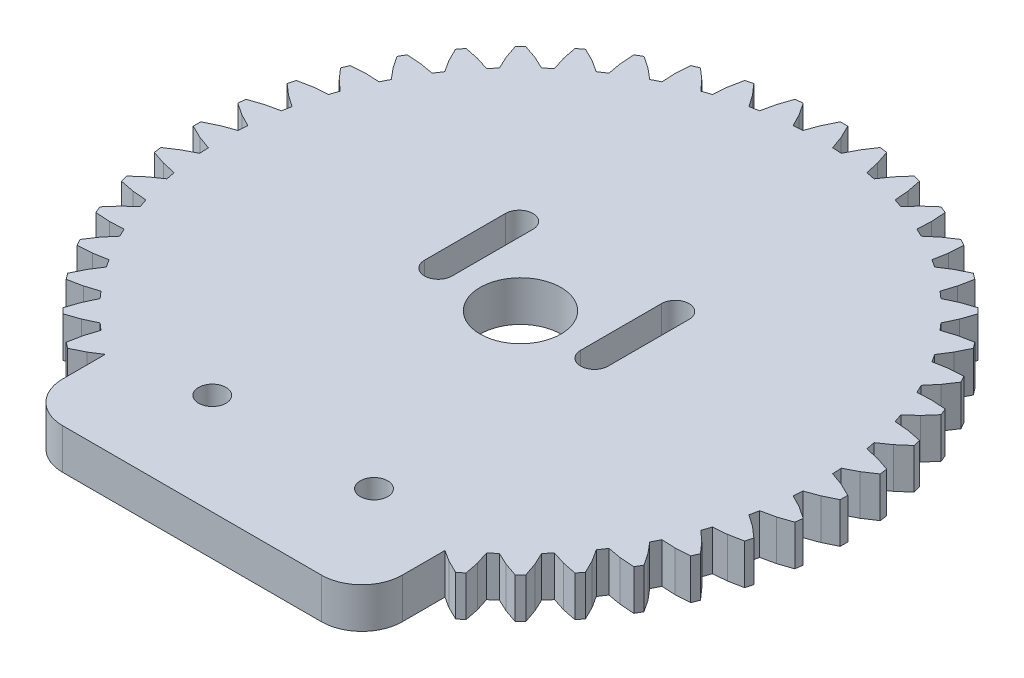
SolidWorks part; units mm, degrees
material "Acrylic (Medium-high impact)"
ref_plane "Front Plane" through (0, 0, 0) normal (0, 0, 1) x (1, 0, 0)
ref_plane "Top Plane" through (0, 0, 0) normal (0, 1, 0) x (1, 0, 0)
ref_plane "Right Plane" through (0, 0, 0) normal (1, 0, 0) x (0, 0, -1)
sketch "Sketch2" plane through (0, 0, 0) normal (0, 1, 0) x (1, 0, 0)
  line L0 (83.8835, 67.191) -> (85.5092, 66.6061)
  line L1 (85.5092, 66.6061) -> (87.1271, 65.8138)
  line L2 (87.1271, 65.8138) -> (87.1271, 64.8854)
  line L3 (87.1271, 64.8854) -> (85.5092, 64.0931)
  line L4 (85.5092, 64.0931) -> (83.8835, 63.5083)
  line L5 (83.8835, 63.5083) -> (83.8095, 62.3776)
  line L6 (83.8095, 62.3776) -> (85.3448, 61.5855)
  line L7 (85.3448, 61.5855) -> (86.8456, 60.5888)
  line L8 (86.8456, 60.5888) -> (86.7243, 59.6683)
  line L9 (86.7243, 59.6683) -> (85.0168, 59.094)
  line L10 (85.0168, 59.094) -> (83.3288, 58.7263)
  line L11 (83.3288, 58.7263) -> (83.1077, 57.615)
  line L12 (83.1077, 57.615) -> (84.5266, 56.6293)
  line L13 (84.5266, 56.6293) -> (85.8844, 55.4453)
  line L14 (85.8844, 55.4453) -> (85.6441, 54.5485)
  line L15 (85.6441, 54.5485) -> (83.8761, 54.202)
  line L16 (83.8761, 54.202) -> (82.1545, 54.0577)
  line L17 (82.1545, 54.0577) -> (81.7903, 52.9848)
  line L18 (81.7903, 52.9848) -> (83.0684, 51.8222)
  line L19 (83.0684, 51.8222) -> (84.26, 50.4711)
  line L20 (84.26, 50.4711) -> (83.9048, 49.6134)
  line L21 (83.9048, 49.6134) -> (82.1066, 49.5006)
  line L22 (82.1066, 49.5006) -> (80.3809, 49.5823)
  line L23 (80.3809, 49.5823) -> (79.8799, 48.5661)
  line L24 (79.8799, 48.5661) -> (80.9952, 47.2468)
  line L25 (80.9952, 47.2468) -> (82.0003, 45.7516)
  line L26 (82.0003, 45.7516) -> (81.5361, 44.9476)
  line L27 (81.5361, 44.9476) -> (79.7387, 45.0704)
  line L28 (79.7387, 45.0704) -> (78.0384, 45.3766)
  line L29 (78.0384, 45.3766) -> (77.4089, 44.4346)
  line L30 (77.4089, 44.4346) -> (78.3426, 42.9809)
  line L31 (78.3426, 42.9809) -> (79.1439, 41.3674)
  line L32 (79.1439, 41.3674) -> (78.5788, 40.6309)
  line L33 (78.5788, 40.6309) -> (76.8128, 40.9873)
  line L34 (76.8128, 40.9873) -> (75.167, 41.5128)
  line L35 (75.167, 41.5128) -> (74.4199, 40.6609)
  line L36 (74.4199, 40.6609) -> (75.1558, 39.0979)
  line L37 (75.1558, 39.0979) -> (75.7397, 37.3936)
  line L38 (75.7397, 37.3936) -> (75.0832, 36.737)
  line L39 (75.0832, 36.737) -> (73.3788, 37.3209)
  line L40 (73.3788, 37.3209) -> (71.8158, 38.0569)
  line L41 (71.8158, 38.0569) -> (70.9639, 37.3097)
  line L42 (70.9639, 37.3097) -> (71.4895, 35.6639)
  line L43 (71.4895, 35.6639) -> (71.8459, 33.898)
  line L44 (71.8459, 33.898) -> (71.1093, 33.3328)
  line L45 (71.1093, 33.3328) -> (69.4958, 34.1341)
  line L46 (69.4958, 34.1341) -> (68.0421, 35.0679)
  line L47 (68.0421, 35.0679) -> (67.1001, 34.4384)
  line L48 (67.1001, 34.4384) -> (67.4064, 32.738)
  line L49 (67.4064, 32.738) -> (67.5292, 30.9407)
  line L50 (67.5292, 30.9407) -> (66.7251, 30.4764)
  line L51 (66.7251, 30.4764) -> (65.23, 31.4815)
  line L52 (65.23, 31.4815) -> (63.9107, 32.5969)
  line L53 (63.9107, 32.5969) -> (62.8945, 32.0958)
  line L54 (62.8945, 32.0958) -> (62.9762, 30.3701)
  line L55 (62.9762, 30.3701) -> (62.8633, 28.572)
  line L56 (62.8633, 28.572) -> (62.0056, 28.2167)
  line L57 (62.0056, 28.2167) -> (60.6545, 29.4083)
  line L58 (60.6545, 29.4083) -> (59.4919, 30.6864)
  line L59 (59.4919, 30.6864) -> (58.419, 30.3222)
  line L60 (58.419, 30.3222) -> (58.2748, 28.6006)
  line L61 (58.2748, 28.6006) -> (57.9283, 26.8327)
  line L62 (57.9283, 26.8327) -> (57.0315, 26.5924)
  line L63 (57.0315, 26.5924) -> (55.8474, 27.9502)
  line L64 (55.8474, 27.9502) -> (54.8618, 29.369)
  line L65 (54.8618, 29.369) -> (53.7504, 29.1479)
  line L66 (53.7504, 29.1479) -> (53.3827, 27.4599)
  line L67 (53.3827, 27.4599) -> (52.8084, 25.7524)
  line L68 (52.8084, 25.7524) -> (51.888, 25.6311)
  line L69 (51.888, 25.6311) -> (50.8913, 27.1319)
  line L70 (50.8913, 27.1319) -> (50.0992, 28.6672)
  line L71 (50.0992, 28.6672) -> (48.9685, 28.5932)
  line L72 (48.9685, 28.5932) -> (48.3836, 26.9675)
  line L73 (48.3836, 26.9675) -> (47.5914, 25.3496)
  line L74 (47.5914, 25.3496) -> (46.6629, 25.3496)
  line L75 (46.6629, 25.3496) -> (45.8707, 26.9675)
  line L76 (45.8707, 26.9675) -> (45.2858, 28.5932)
  line L77 (45.2858, 28.5932) -> (44.1551, 28.6672)
  line L78 (44.1551, 28.6672) -> (43.363, 27.1319)
  line L79 (43.363, 27.1319) -> (42.3663, 25.6311)
  line L80 (42.3663, 25.6311) -> (41.4459, 25.7524)
  line L81 (41.4459, 25.7524) -> (40.8715, 27.4599)
  line L82 (40.8715, 27.4599) -> (40.5038, 29.1479)
  line L83 (40.5038, 29.1479) -> (39.3925, 29.369)
  line L84 (39.3925, 29.369) -> (38.4068, 27.9502)
  line L85 (38.4068, 27.9502) -> (37.2228, 26.5924)
  line L86 (37.2228, 26.5924) -> (36.326, 26.8327)
  line L87 (36.326, 26.8327) -> (35.9795, 28.6006)
  line L88 (35.9795, 28.6006) -> (35.8352, 30.3222)
  line L89 (35.8352, 30.3222) -> (34.7624, 30.6864)
  line L90 (34.7624, 30.6864) -> (33.5998, 29.4083)
  line L91 (33.5998, 29.4083) -> (32.2487, 28.2167)
  line L92 (32.2487, 28.2167) -> (31.3909, 28.572)
  line L93 (31.3909, 28.572) -> (31.2781, 30.3701)
  line L94 (31.2781, 30.3701) -> (31.3598, 32.0958)
  line L95 (31.3598, 32.0958) -> (30.3436, 32.5969)
  line L96 (30.3436, 32.5969) -> (29.0243, 31.4815)
  line L97 (29.0243, 31.4815) -> (27.5292, 30.4764)
  line L98 (27.5292, 30.4764) -> (26.7251, 30.9407)
  line L99 (26.7251, 30.9407) -> (26.8479, 32.738)
  line L100 (26.8479, 32.738) -> (27.1541, 34.4384)
  line L101 (27.1541, 34.4384) -> (26.2121, 35.0679)
  line L102 (26.2121, 35.0679) -> (24.7585, 34.1341)
  line L103 (24.7585, 34.1341) -> (23.1449, 33.3328)
  line L104 (23.1449, 33.3328) -> (22.4084, 33.898)
  line L105 (22.4084, 33.898) -> (22.7648, 35.6639)
  line L106 (22.7648, 35.6639) -> (23.2904, 37.3097)
  line L107 (23.2904, 37.3097) -> (22.4384, 38.0569)
  line L108 (22.4384, 38.0569) -> (20.8754, 37.3209)
  line L109 (20.8754, 37.3209) -> (19.1711, 36.737)
  line L110 (19.1711, 36.737) -> (18.5146, 37.3936)
  line L111 (18.5146, 37.3936) -> (19.0984, 39.0979)
  line L112 (19.0984, 39.0979) -> (19.8344, 40.6609)
  line L113 (19.8344, 40.6609) -> (19.0872, 41.5128)
  line L114 (19.0872, 41.5128) -> (17.4414, 40.9873)
  line L115 (17.4414, 40.9873) -> (15.6755, 40.6309)
  line L116 (15.6755, 40.6309) -> (15.1103, 41.3674)
  line L117 (15.1103, 41.3674) -> (15.9116, 42.9809)
  line L118 (15.9116, 42.9809) -> (16.8454, 44.4346)
  line L119 (16.8454, 44.4346) -> (16.2159, 45.3766)
  line L120 (16.2159, 45.3766) -> (14.5155, 45.0704)
  line L121 (14.5155, 45.0704) -> (12.7182, 44.9476)
  line L122 (12.7182, 44.9476) -> (12.2539, 45.7516)
  line L123 (12.2539, 45.7516) -> (13.2591, 47.2468)
  line L124 (13.2591, 47.2468) -> (14.3744, 48.5661)
  line L125 (14.3744, 48.5661) -> (13.8733, 49.5823)
  line L126 (13.8733, 49.5823) -> (12.1476, 49.5006)
  line L127 (12.1476, 49.5006) -> (10.3495, 49.6134)
  line L128 (10.3495, 49.6134) -> (9.9942, 50.4711)
  line L129 (9.9942, 50.4711) -> (11.1858, 51.8222)
  line L130 (11.1858, 51.8222) -> (12.4639, 52.9848)
  line L131 (12.4639, 52.9848) -> (12.0997, 54.0577)
  line L132 (12.0997, 54.0577) -> (10.3781, 54.202)
  line L133 (10.3781, 54.202) -> (8.6102, 54.5485)
  line L134 (8.6102, 54.5485) -> (8.3699, 55.4453)
  line L135 (8.3699, 55.4453) -> (9.7277, 56.6293)
  line L136 (9.7277, 56.6293) -> (11.1465, 57.615)
  line L137 (11.1465, 57.615) -> (10.9255, 58.7263)
  line L138 (10.9255, 58.7263) -> (9.2374, 59.094)
  line L139 (9.2374, 59.094) -> (7.5299, 59.6683)
  line L140 (7.5299, 59.6683) -> (7.4086, 60.5888)
  line L141 (7.4086, 60.5888) -> (8.9094, 61.5855)
  line L142 (8.9094, 61.5855) -> (10.4448, 62.3776)
  line L143 (10.4448, 62.3776) -> (10.3707, 63.5083)
  line L144 (10.3707, 63.5083) -> (8.745, 64.0931)
  line L145 (8.745, 64.0931) -> (7.1271, 64.8854)
  line L146 (7.1271, 64.8854) -> (7.1271, 65.8138)
  line L147 (7.1271, 65.8138) -> (8.745, 66.6061)
  line L148 (8.745, 66.6061) -> (10.3707, 67.191)
  line L149 (10.3707, 67.191) -> (10.4448, 68.3216)
  line L150 (10.4448, 68.3216) -> (8.9094, 69.1138)
  line L151 (8.9094, 69.1138) -> (7.4086, 70.1105)
  line L152 (7.4086, 70.1105) -> (7.5299, 71.0309)
  line L153 (7.5299, 71.0309) -> (9.2374, 71.6052)
  line L154 (9.2374, 71.6052) -> (10.9255, 71.9729)
  line L155 (10.9255, 71.9729) -> (11.1465, 73.0842)
  line L156 (11.1465, 73.0842) -> (9.7277, 74.0699)
  line L157 (9.7277, 74.0699) -> (8.3699, 75.254)
  line L158 (8.3699, 75.254) -> (8.6102, 76.1508)
  line L159 (8.6102, 76.1508) -> (10.3781, 76.4973)
  line L160 (10.3781, 76.4973) -> (12.0997, 76.6415)
  line L161 (12.0997, 76.6415) -> (12.4639, 77.7144)
  line L162 (12.4639, 77.7144) -> (11.1858, 78.877)
  line L163 (11.1858, 78.877) -> (9.9942, 80.2281)
  line L164 (9.9942, 80.2281) -> (10.3495, 81.0858)
  line L165 (10.3495, 81.0858) -> (12.1476, 81.1987)
  line L166 (12.1476, 81.1987) -> (13.8733, 81.117)
  line L167 (13.8733, 81.117) -> (14.3744, 82.1332)
  line L168 (14.3744, 82.1332) -> (13.2591, 83.4525)
  line L169 (13.2591, 83.4525) -> (12.2539, 84.9476)
  line L170 (12.2539, 84.9476) -> (12.7182, 85.7516)
  line L171 (12.7182, 85.7516) -> (14.5155, 85.6289)
  line L172 (14.5155, 85.6289) -> (16.2159, 85.3226)
  line L173 (16.2159, 85.3226) -> (16.8454, 86.2646)
  line L174 (16.8454, 86.2646) -> (15.9116, 87.7183)
  line L175 (15.9116, 87.7183) -> (15.1103, 89.3318)
  line L176 (15.1103, 89.3318) -> (15.6755, 90.0684)
  line L177 (15.6755, 90.0684) -> (17.4414, 89.712)
  line L178 (17.4414, 89.712) -> (19.0872, 89.1864)
  line L179 (19.0872, 89.1864) -> (19.8344, 90.0383)
  line L180 (19.8344, 90.0383) -> (19.0984, 91.6013)
  line L181 (19.0984, 91.6013) -> (18.5146, 93.3057)
  line L182 (18.5146, 93.3057) -> (19.1711, 93.9622)
  line L183 (19.1711, 93.9622) -> (20.8754, 93.3783)
  line L184 (20.8754, 93.3783) -> (22.4384, 92.6424)
  line L185 (22.4384, 92.6424) -> (23.2904, 93.3895)
  line L186 (23.2904, 93.3895) -> (22.7648, 95.0353)
  line L187 (22.7648, 95.0353) -> (22.4084, 96.8013)
  line L188 (22.4084, 96.8013) -> (23.1449, 97.3664)
  line L189 (23.1449, 97.3664) -> (24.7585, 96.5651)
  line L190 (24.7585, 96.5651) -> (26.2121, 95.6314)
  line L191 (26.2121, 95.6314) -> (27.1541, 96.2609)
  line L192 (27.1541, 96.2609) -> (26.8479, 97.9612)
  line L193 (26.8479, 97.9612) -> (26.7251, 99.7586)
  line L194 (26.7251, 99.7586) -> (27.5292, 100.2228)
  line L195 (27.5292, 100.2228) -> (29.0243, 99.2177)
  line L196 (29.0243, 99.2177) -> (30.3436, 98.1023)
  line L197 (30.3436, 98.1023) -> (31.3598, 98.6034)
  line L198 (31.3598, 98.6034) -> (31.2781, 100.3291)
  line L199 (31.2781, 100.3291) -> (31.3909, 102.1272)
  line L200 (31.3909, 102.1272) -> (32.2487, 102.4825)
  line L201 (32.2487, 102.4825) -> (33.5998, 101.2909)
  line L202 (33.5998, 101.2909) -> (34.7624, 100.0128)
  line L203 (34.7624, 100.0128) -> (35.8352, 100.377)
  line L204 (35.8352, 100.377) -> (35.9795, 102.0986)
  line L205 (35.9795, 102.0986) -> (36.326, 103.8666)
  line L206 (36.326, 103.8666) -> (37.2228, 104.1068)
  line L207 (37.2228, 104.1068) -> (38.4068, 102.7491)
  line L208 (38.4068, 102.7491) -> (39.3925, 101.3302)
  line L209 (39.3925, 101.3302) -> (40.5038, 101.5513)
  line L210 (40.5038, 101.5513) -> (40.8715, 103.2393)
  line L211 (40.8715, 103.2393) -> (41.4459, 104.9468)
  line L212 (41.4459, 104.9468) -> (42.3663, 105.0681)
  line L213 (42.3663, 105.0681) -> (43.363, 103.5673)
  line L214 (43.363, 103.5673) -> (44.1551, 102.032)
  line L215 (44.1551, 102.032) -> (45.2858, 102.106)
  line L216 (45.2858, 102.106) -> (45.8707, 103.7317)
  line L217 (45.8707, 103.7317) -> (46.6629, 105.3496)
  line L218 (46.6629, 105.3496) -> (47.5914, 105.3496)
  line L219 (47.5914, 105.3496) -> (48.3836, 103.7317)
  line L220 (48.3836, 103.7317) -> (48.9685, 102.106)
  line L221 (48.9685, 102.106) -> (50.0992, 102.032)
  line L222 (50.0992, 102.032) -> (50.8913, 103.5673)
  line L223 (50.8913, 103.5673) -> (51.888, 105.0681)
  line L224 (51.888, 105.0681) -> (52.8084, 104.9468)
  line L225 (52.8084, 104.9468) -> (53.3827, 103.2393)
  line L226 (53.3827, 103.2393) -> (53.7504, 101.5513)
  line L227 (53.7504, 101.5513) -> (54.8618, 101.3302)
  line L228 (54.8618, 101.3302) -> (55.8474, 102.7491)
  line L229 (55.8474, 102.7491) -> (57.0315, 104.1068)
  line L230 (57.0315, 104.1068) -> (57.9283, 103.8666)
  line L231 (57.9283, 103.8666) -> (58.2748, 102.0986)
  line L232 (58.2748, 102.0986) -> (58.419, 100.377)
  line L233 (58.419, 100.377) -> (59.4919, 100.0128)
  line L234 (59.4919, 100.0128) -> (60.6545, 101.2909)
  line L235 (60.6545, 101.2909) -> (62.0056, 102.4825)
  line L236 (62.0056, 102.4825) -> (62.8633, 102.1272)
  line L237 (62.8633, 102.1272) -> (62.9762, 100.3291)
  line L238 (62.9762, 100.3291) -> (62.8945, 98.6034)
  line L239 (62.8945, 98.6034) -> (63.9107, 98.1023)
  line L240 (63.9107, 98.1023) -> (65.23, 99.2177)
  line L241 (65.23, 99.2177) -> (66.7251, 100.2228)
  line L242 (66.7251, 100.2228) -> (67.5292, 99.7586)
  line L243 (67.5292, 99.7586) -> (67.4064, 97.9612)
  line L244 (67.4064, 97.9612) -> (67.1001, 96.2609)
  line L245 (67.1001, 96.2609) -> (68.0421, 95.6314)
  line L246 (68.0421, 95.6314) -> (69.4958, 96.5651)
  line L247 (69.4958, 96.5651) -> (71.1093, 97.3664)
  line L248 (71.1093, 97.3664) -> (71.8459, 96.8013)
  line L249 (71.8459, 96.8013) -> (71.4895, 95.0353)
  line L250 (71.4895, 95.0353) -> (70.9639, 93.3895)
  line L251 (70.9639, 93.3895) -> (71.8158, 92.6424)
  line L252 (71.8158, 92.6424) -> (73.3788, 93.3783)
  line L253 (73.3788, 93.3783) -> (75.0832, 93.9622)
  line L254 (75.0832, 93.9622) -> (75.7397, 93.3057)
  line L255 (75.7397, 93.3057) -> (75.1558, 91.6013)
  line L256 (75.1558, 91.6013) -> (74.4199, 90.0383)
  line L257 (74.4199, 90.0383) -> (75.167, 89.1864)
  line L258 (75.167, 89.1864) -> (76.8128, 89.712)
  line L259 (76.8128, 89.712) -> (78.5788, 90.0684)
  line L260 (78.5788, 90.0684) -> (79.1439, 89.3318)
  line L261 (79.1439, 89.3318) -> (78.3426, 87.7183)
  line L262 (78.3426, 87.7183) -> (77.4089, 86.2646)
  line L263 (77.4089, 86.2646) -> (78.0384, 85.3226)
  line L264 (78.0384, 85.3226) -> (79.7387, 85.6289)
  line L265 (79.7387, 85.6289) -> (81.5361, 85.7516)
  line L266 (81.5361, 85.7516) -> (82.0003, 84.9476)
  line L267 (82.0003, 84.9476) -> (80.9952, 83.4525)
  line L268 (80.9952, 83.4525) -> (79.8799, 82.1332)
  line L269 (79.8799, 82.1332) -> (80.3809, 81.117)
  line L270 (80.3809, 81.117) -> (82.1066, 81.1987)
  line L271 (82.1066, 81.1987) -> (83.9048, 81.0858)
  line L272 (83.9048, 81.0858) -> (84.26, 80.2281)
  line L273 (84.26, 80.2281) -> (83.0684, 78.877)
  line L274 (83.0684, 78.877) -> (81.7903, 77.7144)
  line L275 (81.7903, 77.7144) -> (82.1545, 76.6415)
  line L276 (82.1545, 76.6415) -> (83.8761, 76.4973)
  line L277 (83.8761, 76.4973) -> (85.6441, 76.1508)
  line L278 (85.6441, 76.1508) -> (85.8844, 75.254)
  line L279 (85.8844, 75.254) -> (84.5266, 74.0699)
  line L280 (84.5266, 74.0699) -> (83.1077, 73.0842)
  line L281 (83.1077, 73.0842) -> (83.3288, 71.9729)
  line L282 (83.3288, 71.9729) -> (85.0168, 71.6052)
  line L283 (85.0168, 71.6052) -> (86.7243, 71.0309)
  line L284 (86.7243, 71.0309) -> (86.8456, 70.1105)
  line L285 (86.8456, 70.1105) -> (85.3448, 69.1138)
  line L286 (85.3448, 69.1138) -> (83.8095, 68.3216)
  line L287 (83.8095, 68.3216) -> (83.8835, 67.191)
  line L288 (47.1271, 105.3496) -> (47.1271, 25.3496) construction
  line L289 (7.1271, 65.3496) -> (87.1271, 65.3496) construction
  circle A0 centre (47.1271, 65.3496) radius 5
  point P292 (47.1271, 65.3496)
  dimension "D1" = 10
sketch "Sketch7" plane through (0, 0, 0) normal (0, 1, 0) x (1, 0, 0)
  line L0 (47.1271, 65.3496) -> (47.1271, 5.5554) construction
  line L1 (47.1271, 105.3496) -> (47.1271, 25.3496) construction
  circle A0 centre (37.1271, 37.2366) radius 1.7
  circle A1 centre (57.1271, 37.2366) radius 1.7
  dimension "D3" = 3.4
  dimension "D1" = 20
  dimension "D2" = 28.113
sketch "Sketch8" plane through (0, 0, 0) normal (0, 1, 0) x (1, 0, 0)
  line L0 (37.1271, 37.2366) -> (57.1271, 37.2366) construction
  line L2 (26.1271, 49.7366) -> (68.1271, 49.7366)
  line L3 (26.1271, 49.7366) -> (26.1271, 24.7366)
  line L4 (26.1271, 24.7366) -> (68.1271, 24.7366)
  line L5 (68.1271, 49.7366) -> (68.1271, 24.7366)
  line L6 (26.1271, 49.7366) -> (68.1271, 24.7366) construction
  line L7 (26.1271, 24.7366) -> (68.1271, 49.7366) construction
  point P4 (47.1271, 37.2366)
  dimension "D1" = 42
  dimension "D2" = 25
extrude "Boss-Extrude3" add sketch "Sketch2" along normal blind 5
extrude "Boss-Extrude4" add sketch "Sketch8" along normal up to surface (5 mm away) up to face at (47.1271, 5, -65.3496)
extrude "Cut-Extrude1" cut sketch "Sketch7" along normal through all
sketch "Sketch10" plane through (0, 0, 0) normal (0, -1, 0) x (1, 0, 0)
  line L0 (37.4771, -64.8366) -> (37.4771, -74.8366) construction
  line L1 (39.1771, -64.8366) -> (39.1771, -74.8366)
  line L2 (35.7771, -64.8366) -> (35.7771, -74.8366)
  line L3 (56.7771, -64.8366) -> (56.7771, -74.8366) construction
  line L4 (58.4771, -64.8366) -> (58.4771, -74.8366)
  line L5 (55.0771, -64.8366) -> (55.0771, -74.8366)
  circle A0 centre (56.7771, -69.8366) radius 1.7
  circle A1 centre (37.4771, -69.8366) radius 1.7
  circle A2 centre (37.4771, -69.8366) radius 1.7 construction
  circle A3 centre (56.7771, -69.8366) radius 1.7 construction
  arc A4 (39.1771, -64.8366) -> (35.7771, -64.8366) centre (37.4771, -64.8366) ccw
  arc A5 (35.7771, -74.8366) -> (39.1771, -74.8366) centre (37.4771, -74.8366) ccw
  arc A6 (58.4771, -64.8366) -> (55.0771, -64.8366) centre (56.7771, -64.8366) ccw
  arc A7 (55.0771, -74.8366) -> (58.4771, -74.8366) centre (56.7771, -74.8366) ccw
  point P8 (37.4771, -69.8366)
  point P19 (56.7771, -69.8366)
  dimension "D1" = 10
extrude "Cut-Extrude2" cut sketch "Sketch10" against normal up to next contours L1 A4 L2 A1 | A1 | L2 A5 L1 A1 | L4 A6 L5 A0 | A0 | L5 A7 L4 A0 region at (37.4771, 0, -66.0014) region at (37.4771, 0, -69.8366) region at (37.4771, 0, -73.6718) region at (56.7771, 0, -66.0014) region at (56.7771, 0, -69.8366) region at (56.7771, 0, -73.6718)
fillet "Fillet1" radius 5 2 edges at (68.1271, 2.5, -24.7366) (26.1271, 2.5, -24.7366)
ref_axis "Axis5" through (47.1271, 5, -65.3496) along (0, -1, 0)
